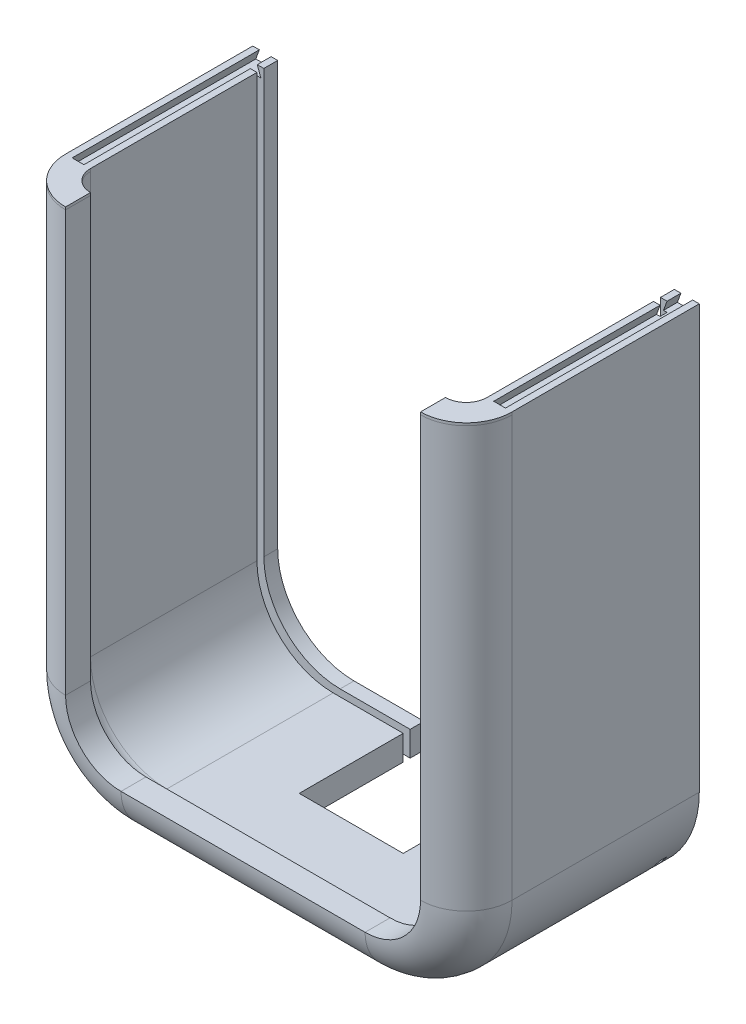
SolidWorks part; units mm, degrees
ref_plane "前基準面" through (0, 0, 0) normal (0, 0, 1) x (1, 0, 0)
ref_plane "上基準面" through (0, 0, 0) normal (0, 1, 0) x (1, 0, 0)
ref_plane "右基準面" through (0, 0, 0) normal (1, 0, 0) x (0, 0, -1)
sketch "草圖1" plane through (0, 0, 0) normal (0, 0, 1) x (1, 0, 0)
  line L0 (-17.6, -33.6594) -> (17.6, -33.6594)
  line L1 (28.6, -22.6594) -> (28.6, 38.3406)
  line L5 (32.2, 38.3406) -> (32.2, -22.6594)
  line L6 (17.6, -37.2594) -> (-17.6, -37.2594)
  line L8 (0, -100.7851) -> (0, -37.2594) construction
  line L9 (-32.2, 38.3406) -> (-32.2, -22.6594)
  line L11 (-28.6, -22.6594) -> (-28.6, 38.3406)
  line L12 (0, -33.6594) -> (0, 51.5702) construction
  line L13 (28.6, 38.3406) -> (29.55, 38.3406)
  line L14 (30.4, 35.3783) -> (30.4, 40.518) construction
  line L19 (31.25, 38.3406) -> (32.2, 38.3406)
  line L20 (-31.25, 38.3406) -> (-32.2, 38.3406)
  line L24 (-28.6, 38.3406) -> (-29.55, 38.3406)
  line L45 (29.55, 38.3406) -> (29.0404, 36.9406)
  line L46 (29.0404, 36.9406) -> (31.7596, 36.9406)
  line L47 (31.25, 38.3406) -> (31.7596, 36.9406)
  line L48 (-31.25, 38.3406) -> (-31.7596, 36.9406)
  line L49 (-29.0404, 36.9406) -> (-31.7596, 36.9406)
  line L50 (-29.55, 38.3406) -> (-29.0404, 36.9406)
  line L51 (-42.4604, -22.6594) -> (-12.767, -22.6594) construction
  line L53 (13.6271, -22.6594) -> (34.6141, -22.6594) construction
  line L54 (-17.6, -37.9298) -> (-17.6, -20.0121) construction
  line L55 (17.6, -43.3032) -> (17.6, -18.8337) construction
  arc A0 (28.6, -22.6594) -> (17.6, -33.6594) centre (17.6, -22.6594) cw
  arc A3 (-28.6, -22.6594) -> (-17.6, -33.6594) centre (-17.6, -22.6594) ccw
  arc A4 (-32.2, -22.6594) -> (-17.6, -37.2594) centre (-17.6, -22.6594) ccw
  arc A5 (32.2, -22.6594) -> (17.6, -37.2594) centre (17.6, -22.6594) cw
  point P6 (28.6, -33.6594)
  point P12 (32.2, -37.2594)
  point P23 (-32.2, -37.2594)
  point P24 (-28.6, -33.6594)
  point P33 (30.4, 36.9406)
  point P38 (-28.6, 38.751)
  dimension "D2" = 11
  dimension "D6" = 61
  dimension "D1" = 70
  dimension "D3" = 1.4
  dimension "D4" = 3.6
  dimension "D5" = 72
  dimension "D7" = 3.6
  dimension "D8" = 1.8
  dimension "D9" = 28.6
  dimension "D10" = 0.85
extrude "填料-伸長1" add sketch "草圖1" along normal blind 27
ref_plane "平面1" through (0, 0, 3) normal (0, 0, 1) x (1, 0, 0)
sketch "草圖3" plane through (0, 0, 3) normal (0, 0, 1) x (1, 0, 0)
  line L0 (-28.6, 38.3406) -> (-28.6, -22.6594)
  line L1 (-17.6, -33.6594) -> (17.6, -33.6594)
  line L3 (28.6, 38.3406) -> (28.6, -22.6594)
  line L4 (-29.56, 38.3406) -> (-29.56, -22.6594)
  line L6 (29.56, 38.3406) -> (29.56, -22.6594)
  line L7 (-29.56, 38.3406) -> (-28.6, 38.3406)
  line L8 (28.6, 38.3406) -> (29.56, 38.3406)
  line L9 (-17.6, -34.6194) -> (17.6, -34.6194) construction
  line L16 (-29.56, -22.6594) -> (-29.56, -37.2594)
  line L17 (0, 10.7904) -> (0, -51.8508) construction
  line L18 (29.56, -22.6594) -> (29.56, -37.2594)
  line L19 (-29.56, -37.2594) -> (29.56, -37.2594)
  arc A0 (-17.6, -33.6594) -> (-28.6, -22.6594) centre (-17.6, -22.6594) cw
  arc A1 (28.6, -22.6594) -> (17.6, -33.6594) centre (17.6, -22.6594) cw
  arc A4 (-17.6, -34.6194) -> (-29.56, -22.6594) centre (-17.6, -22.6594) cw construction
  arc A5 (29.56, -22.6594) -> (17.6, -34.6194) centre (17.6, -22.6594) cw construction
  dimension "D1" = 11
  dimension "D2" = 0.96
extrude "除料-伸長1" cut sketch "草圖3" against normal blind 1
ref_plane "平面2" through (0, 0, 5) normal (0, 0, 1) x (1, 0, 0)
sketch "草圖4" plane through (0, 0, 5) normal (0, 0, 1) x (1, 0, 0)
  line L0 (0, -29.7594) -> (0, -44.7594) construction
  line L1 (-17.6, -37.2594) -> (17.6, -37.2594) construction
  line L2 (-7.5, -37.2594) -> (7.5, -37.2594)
  line L3 (-7.5, -37.2594) -> (-7.5, -33.6594)
  line L4 (-7.5, -33.6594) -> (7.5, -33.6594)
  line L5 (7.5, -37.2594) -> (7.5, -33.6594)
  line L6 (17.6, -33.6594) -> (-17.6, -33.6594) construction
  point P11 (0, -37.2594)
  dimension "D1" = 15
extrude "除料-伸長2" cut sketch "草圖4" against normal through all
sketch "草圖6" plane through (0, 0, 27) normal (0, 0, 1) x (1, 0, 0)
  line L0 (-30.4, 37.9687) -> (-30.4, -22.6594)
  line L1 (-17.6, -35.4594) -> (17.6, -35.4594)
  line L2 (30.4, 37.9687) -> (30.4, -22.6594)
  line L3 (-17.6, -37.2594) -> (17.6, -37.2594) construction
  line L5 (-30.4, 37.9687) -> (-30.4, 38.3406)
  line L6 (30.4, 37.9687) -> (30.4, 38.3406)
  line L9 (-34.3425, -22.6594) -> (-15.9262, -22.6594) construction
  line L10 (-17.6, -20.1995) -> (-17.6, -41.8303) construction
  line L11 (14.2565, -22.6594) -> (39.153, -22.6594) construction
  line L12 (17.6, -18.3707) -> (17.6, -46.1516) construction
  arc A0 (-30.4, -22.6594) -> (-17.6, -35.4594) centre (-17.6, -22.6594) ccw
  arc A1 (30.4, -22.6594) -> (17.6, -35.4594) centre (17.6, -22.6594) cw
  dimension "D1" = 1.8
sketch "草圖7" plane through (0, 36.9406, 0) normal (0, 1, 0) x (1, 0, 0)
  line L1 (17.6, -27) -> (30.4, -27) construction
  line L3 (-32.2, -27) -> (-28.6, -27)
  line L4 (-25.6, -30) -> (-25.6, -33.6)
  arc A0 (-25.6, -30) -> (-28.6, -27) centre (-25.6, -27) cw
  arc A1 (-32.2, -27) -> (-25.6, -33.6) centre (-25.6, -27) ccw
  dimension "D1" = 3
  dimension "D2" = 3
sweep "掃出4" add profiles "草圖7" path "草圖6"
extrude "除料-伸長3" cut sketch "草圖4<2>" along normal blind 13
sketch "草圖4<2>" plane through (0, 0, 5) normal (0, 0, 1) x (1, 0, 0) same geometry as "草圖4"
